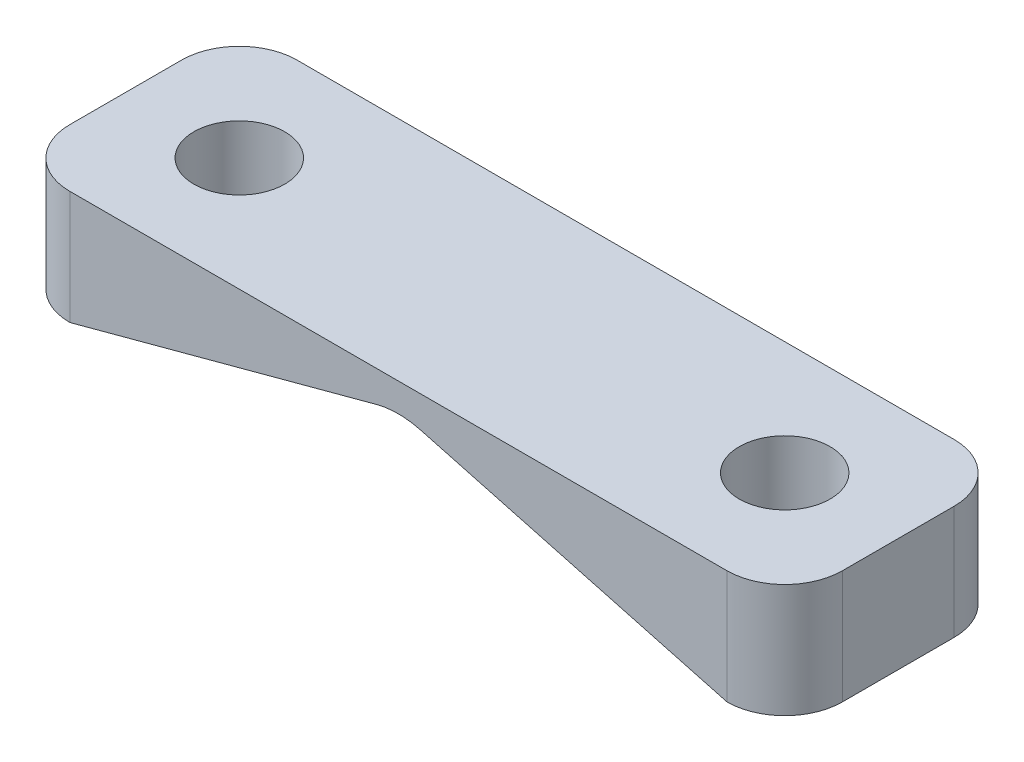
SolidWorks part; units mm, degrees
ref_plane "Front Plane" through (0, 0, 0) normal (0, 0, 1) x (1, 0, 0)
ref_plane "Top Plane" through (0, 0, 0) normal (0, 1, 0) x (1, 0, 0)
ref_plane "Right Plane" through (0, 0, 0) normal (1, 0, 0) x (0, 0, -1)
sketch "Sketch1" plane through (0, 0, 0) normal (0, 0, 1) x (1, 0, 0)
  line L1 (0, 0) -> (34, 0)
  line L2 (0, 0) -> (0, 5)
  line L3 (0, 5) -> (34, 5)
  line L4 (34, 0) -> (34, 5)
  dimension "D1" = 34
  dimension "D2" = 5
extrude "Boss-Extrude1" add sketch "Sketch1" along normal blind 10
sketch "Sketch2" plane through (0, 0, 10) normal (0, 0, 1) x (1, 0, 0)
  line L0 (0, 0) -> (34, 0) construction
  circle A0 centre (17, 0) radius 3.75
  dimension "D1" = 7.5
extrude "Cut-Extrude1" cut sketch "Sketch2" against normal through all both and the other way through all
fillet "Fillet1" radius 2.54 4 edges at (0, 2.5, 0) (34, 2.5, 0) (34, 2.5, 10) (0, 2.5, 10)
sketch "Sketch3" plane through (0, 5, 0) normal (0, 1, 0) x (1, 0, 0)
  line L0 (0, -5) -> (5, -5)
  line L1 (0, -7.46) -> (0, -2.54) construction
  line L2 (5, -5) -> (29, -5)
  line L3 (29, -5) -> (34, -5)
  line L4 (34, -7.46) -> (34, -2.54) construction
  point P9 (5, -5)
  point P10 (29, -5)
  dimension "D1" = 5
  dimension "D2" = 5
hole_wizard "Ø4.0mm Dowel Hole1" positions "Sketch4" profile "Sketch5" hole size "Ø4.0" standard "ANSI Metric" end condition through all
sketch "Sketch4" plane through (0, 5, 0) normal (0, 1, 0) x (1, 0, 0)
  point P0 (5, -5)
  point P3 (29, -5)
sketch "Sketch5" plane through (5, 5, 5) normal (1, 0, 0) x (0, 0, 1)
  line L0 (0, 0) -> (0, 5)
  line L1 (0, 5) -> (2, 5)
  line L2 (2, 5) -> (2, 0)
  line L5 (2, 0) -> (0, 0)
  line L11 (0, -6.35) -> (0, 107.95) construction
  dimension "Thru Hole Dia." = 4
  dimension "Thru Hole Depth" = 5
sketch "Sketch6" plane through (0, 0, 0) normal (0, 0, -1) x (-1, 0, 0)
  line L0 (-2.54, 0) -> (-16.0423, 3.6256)
  line L1 (-16.0423, 3.6256) -> (-16.0423, 0)
  line L2 (-16.0423, 0) -> (-2.54, 0)
  arc A1 (-13.25, 0) -> (-20.75, 0) centre (-17, 0) ccw construction
extrude "Cut-Extrude2" cut sketch "Sketch6" against normal through all both and the other way through all
sketch "Sketch7" plane through (0, 0, 0) normal (0, -1, 0) x (1, 0, 0)
  line L0 (18.3814, 10) -> (18.3814, 0)
  line L1 (20.75, 10) -> (16.0128, 10) construction
  line L2 (16.0128, 0) -> (20.75, 0) construction
  line L3 (18.3814, 0) -> (30.7341, 0)
  line L4 (20.75, 10) -> (18.3814, 10)
  circle A0 centre (30.7341, 9.9841) radius 9.9841
  line M2 (20.75, 0) -> (31.46, 0)
  line M7 (20.75, 10) -> (20.75, 0)
extrude "Cut-Extrude3" [suppressed] cut sketch "Sketch7" against normal blind 3.5 contours A0 M7 M2 | A0 L4 L0 L3 M7
fillet "Fillet2" [suppressed] radius 2.54
ref_plane "Plane1" through (17, 0, 0) normal (1, 0, 0) x (0, 0, -1)
mirror "Mirror1" about plane through (17, 0, 0) normal (1, 0, 0) of "Cut-Extrude2"
